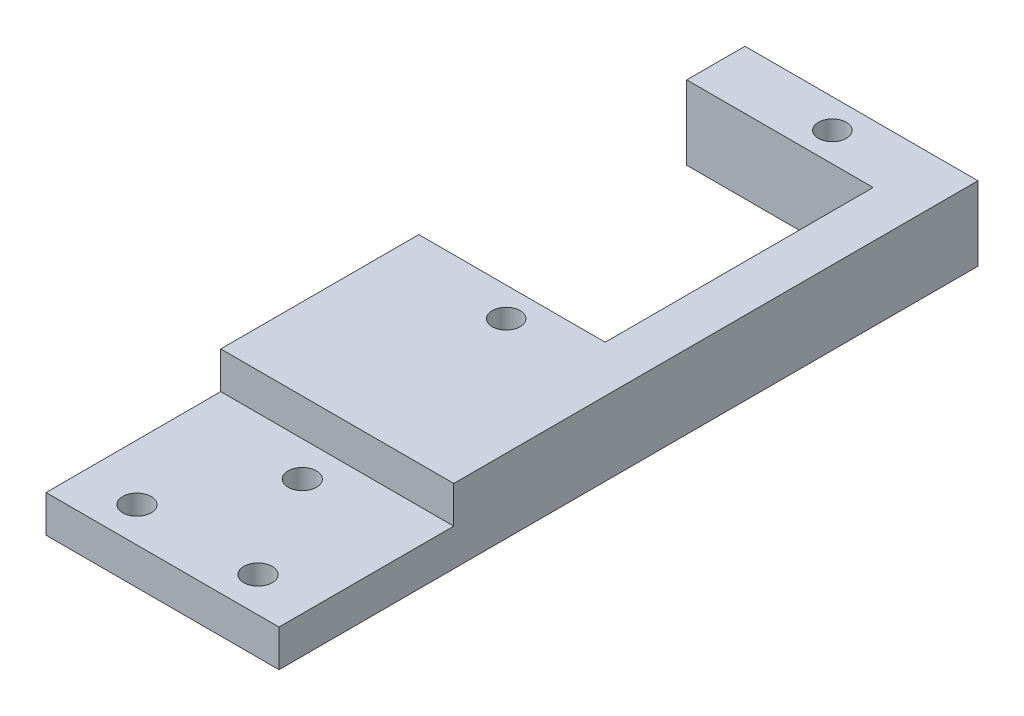
SolidWorks part; units mm, degrees
material "ABS"
ref_plane "Front" through (0, 0, 0) normal (0, 0, 1) x (1, 0, 0)
ref_plane "Top" through (0, 0, 0) normal (0, 1, 0) x (1, 0, 0)
ref_plane "Right" through (0, 0, 0) normal (1, 0, 0) x (0, 0, -1)
sketch "Sketch2" plane through (0, 0, 0) normal (0, 1, 0) x (1, 0, 0)
  line L1 (0, 0) -> (20, 0)
  line L2 (0, 0) -> (0, -60)
  line L3 (0, -60) -> (20, -60)
  line L4 (20, 0) -> (20, -60)
  dimension "D1" = 20
  dimension "D2" = 60
extrude "Boss-Extrude1" add sketch "Sketch2" along normal blind 6.35
sketch "Sketch4" plane through (0, 6.35, 0) normal (0, 1, 0) x (1, 0, 0)
  line L0 (0, 0) -> (0, -60) construction
  line L1 (0, -5) -> (16, -5)
  line L2 (0, -5) -> (0, -28)
  line L3 (0, -28) -> (16, -28)
  line L4 (16, -5) -> (16, -28)
  line L5 (20, -60) -> (20, 0) construction
  line L6 (20, 0) -> (0, 0) construction
  dimension "D1" = 4
  dimension "D2" = 5
  dimension "D3" = 23
extrude "Cut-Extrude1" cut sketch "Sketch4" against normal through all
hole_wizard "M2 Clearance Hole1" positions "Sketch8" profile "Sketch9" hole size "M2" standard "IS" end condition through all
sketch "Sketch8" plane through (0, 6.35, 0) normal (0, 1, 0) x (1, 0, 0)
  line L0 (10, 0) -> (10, -60) construction
  line L1 (20, 0) -> (0, 0) construction
  line L2 (0, -60) -> (20, -60) construction
  line L3 (0, -28) -> (16, -28) construction
  point P9 (10, -2.5)
  point P11 (10, -30.5)
  dimension "D1" = 2.5
  dimension "D2" = 2.5
sketch "Sketch9" plane through (10, 6.35, 30.5) normal (1, 0, 0) x (0, 0, 1)
  line L0 (0, 0) -> (0, 6.35)
  line L1 (0, 6.35) -> (1.2, 6.35)
  line L2 (1.2, 6.35) -> (1.2, 0)
  line L5 (1.2, 0) -> (0, 0)
  line L11 (0, -6.35) -> (0, 107.95) construction
  dimension "Thru Hole Dia." = 2.4
  dimension "Thru Hole Depth" = 6.35
sketch "Sketch10" plane through (20, 0, 0) normal (1, 0, 0) x (0, 0, -1)
  line L0 (-60, 6.35) -> (-60, 0) construction
  line L1 (-60, 6.35) -> (-45, 6.35)
  line L2 (-60, 6.35) -> (-60, 3.175)
  line L3 (-60, 3.175) -> (-45, 3.175)
  line L4 (-45, 6.35) -> (-45, 3.175)
  dimension "D1" = 15
extrude "Cut-Extrude2" cut sketch "Sketch10" against normal through all
sketch "Sketch12" plane through (0, 3.175, 0) normal (0, 1, 0) x (1, 0, 0)
  line L0 (10, -60) -> (10, -45) construction
  line L1 (0, -60) -> (20, -60) construction
  line L2 (0, -45) -> (20, -45) construction
  line L3 (10, -48) -> (15.1962, -57) construction
  line L4 (15.1962, -57) -> (4.8038, -57) construction
  line L5 (4.8038, -57) -> (10, -48) construction
  dimension "D1" = 9
  dimension "D2" = 3
hole_wizard "#2 Clearance Hole1" positions "Sketch13" profile "Sketch14" hole size "#2" standard "ANSI Inch" end condition through all
sketch "Sketch13" plane through (0, 3.175, 0) normal (0, 1, 0) x (1, 0, 0)
  point P0 (10, -48)
  point P3 (4.8038, -57)
  point P6 (15.1962, -57)
sketch "Sketch14" plane through (10, 3.175, 48) normal (1, 0, 0) x (0, 0, 1)
  line L0 (0, 0) -> (0, 3.175)
  line L1 (0, 3.175) -> (1.2192, 3.175)
  line L2 (1.2192, 3.175) -> (1.2192, 0)
  line L5 (1.2192, 0) -> (0, 0)
  line L11 (0, -6.35) -> (0, 107.95) construction
  dimension "Thru Hole Dia." = 2.4384
  dimension "Thru Hole Depth" = 3.175
